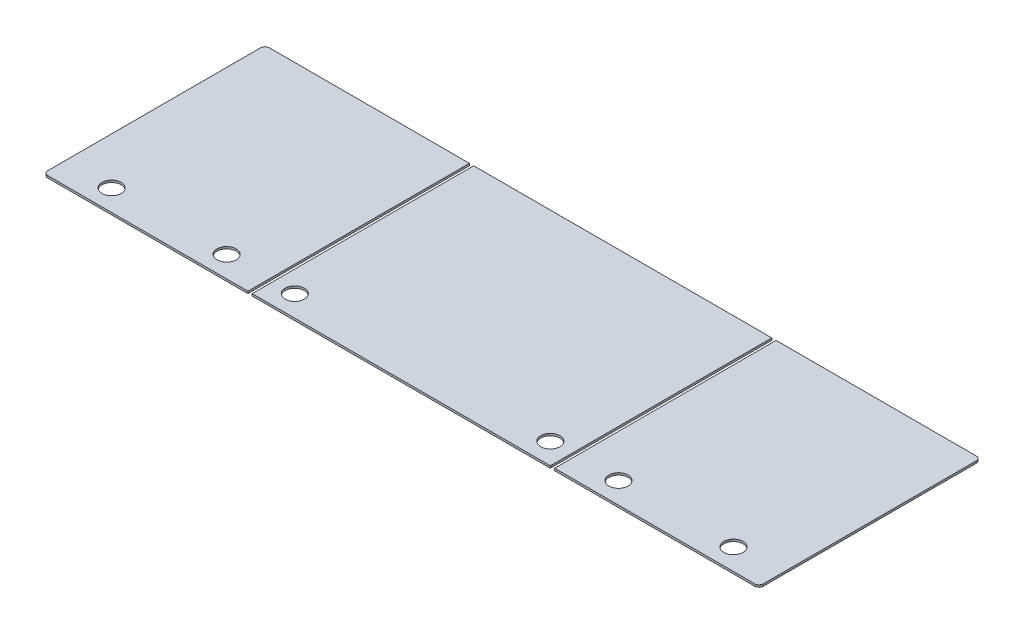
SolidWorks part; units mm, degrees
ref_plane "Front" through (0, 0, 0) normal (0, 0, 1) x (1, 0, 0)
ref_plane "Top" through (0, 0, 0) normal (0, 1, 0) x (1, 0, 0)
ref_plane "Right" through (0, 0, 0) normal (1, 0, 0) x (0, 0, -1)
sketch "Sketch1" plane through (0, 0, 0) normal (0, 1, 0) x (1, 0, 0)
  line L1 (6.35, 0) -> (1060.45, 0)
  line L2 (0, 6.35) -> (0, 323.85)
  line L3 (6.35, 330.2) -> (1060.45, 330.2)
  line L4 (1066.8, 6.35) -> (1066.8, 323.85)
  line L5 (0, 0) -> (1066.8, 330.2) construction
  line L6 (0, 330.2) -> (1066.8, 0) construction
  arc A0 (1060.45, 330.2) -> (1066.8, 323.85) centre (1060.45, 323.85) cw
  arc A1 (1060.45, 0) -> (1066.8, 6.35) centre (1060.45, 6.35) ccw
  arc A2 (6.35, 0) -> (0, 6.35) centre (6.35, 6.35) cw
  arc A3 (0, 323.85) -> (6.35, 330.2) centre (6.35, 323.85) cw
  point P4 (533.4, 165.1)
  dimension "D3" = 6.35
  dimension "D1" = 330.2
  dimension "D2" = 1066.8
extrude "Boss-Extrude1" add sketch "Sketch1" along normal blind 3.175
sketch "Sketch2" plane through (0, 3.175, 0) normal (0, 1, 0) x (1, 0, 0)
  line L0 (1060.45, 330.2) -> (6.35, 330.2) construction
  line L1 (304.8, 330.2) -> (311.15, 330.2)
  line L2 (304.8, 330.2) -> (304.8, 0)
  line L3 (304.8, 0) -> (311.15, 0)
  line L4 (311.15, 330.2) -> (311.15, 0)
  line L5 (304.8, 330.2) -> (311.15, 0) construction
  line L6 (304.8, 0) -> (311.15, 330.2) construction
  line L7 (6.35, 0) -> (1060.45, 0) construction
  line L8 (0, 323.85) -> (0, 6.35) construction
  line L9 (533.4, 330.2) -> (533.4, 0) construction
  line L10 (762, 0) -> (755.65, 330.2) construction
  line L11 (762, 330.2) -> (755.65, 0) construction
  line L12 (755.65, 330.2) -> (755.65, 0)
  line L13 (762, 0) -> (755.65, 0)
  line L14 (762, 330.2) -> (762, 0)
  line L15 (762, 330.2) -> (755.65, 330.2)
  point P4 (307.975, 165.1)
  point P17 (758.825, 165.1)
  dimension "D1" = 6.35
  dimension "D2" = 304.8
extrude "Hing Cuts" cut sketch "Sketch2" against normal up to next
sketch "Sketch3" plane through (0, 3.175, 0) normal (0, 1, 0) x (1, 0, 0)
  line L0 (755.65, 330.2) -> (755.65, 0) construction
  line L2 (311.15, 0) -> (755.65, 0) construction
  line L3 (533.4, 0) -> (533.4, 330.2) construction
  line L4 (755.65, 330.2) -> (311.15, 330.2) construction
  circle A0 centre (723.9, 31.75) radius 14.2875
  circle A1 centre (342.9, 31.75) radius 14.2875
  dimension "D1" = 28.575
  dimension "D2" = 31.75
  dimension "D3" = 31.75
extrude "Holes" cut sketch "Sketch3" against normal up to next (3.175 mm away)
sketch "Sketch4" plane through (0, 3.175, 0) normal (0, 1, 0) x (1, 0, 0)
  line L0 (723.9, 31.75) -> (1051.0906, 31.75) construction
  line L1 (762, 0) -> (762, 330.2) construction
  line L2 (911.225, 0) -> (911.225, -45.9905) construction
  line L3 (762, 0) -> (1060.45, 0) construction
  circle A0 centre (825.5, 31.75) radius 14.2875
  circle A1 centre (723.9, 31.75) radius 14.2875 construction
  circle A2 centre (996.95, 31.75) radius 14.2875
  dimension "D1" = 63.5
extrude "Cut-Extrude3" cut sketch "Sketch4" against normal up to next (3.175 mm away)
sketch "Sketch5" plane through (0, 3.175, 0) normal (0, 1, 0) x (1, 0, 0)
  line L0 (342.9, 31.75) -> (17.9445, 31.75) construction
  line L1 (304.8, 330.2) -> (304.8, 0) construction
  line L2 (155.575, 0) -> (155.575, -70.5202) construction
  line L3 (6.35, 0) -> (304.8, 0) construction
  circle A0 centre (241.3, 31.75) radius 14.2875
  circle A1 centre (342.9, 31.75) radius 14.2875 construction
  circle A2 centre (69.85, 31.75) radius 14.2875
  point P13 (155.575, -70.5202)
  dimension "D1" = 63.5
extrude "Cut-Extrude4" cut sketch "Sketch5" against normal up to next (3.175 mm away)
